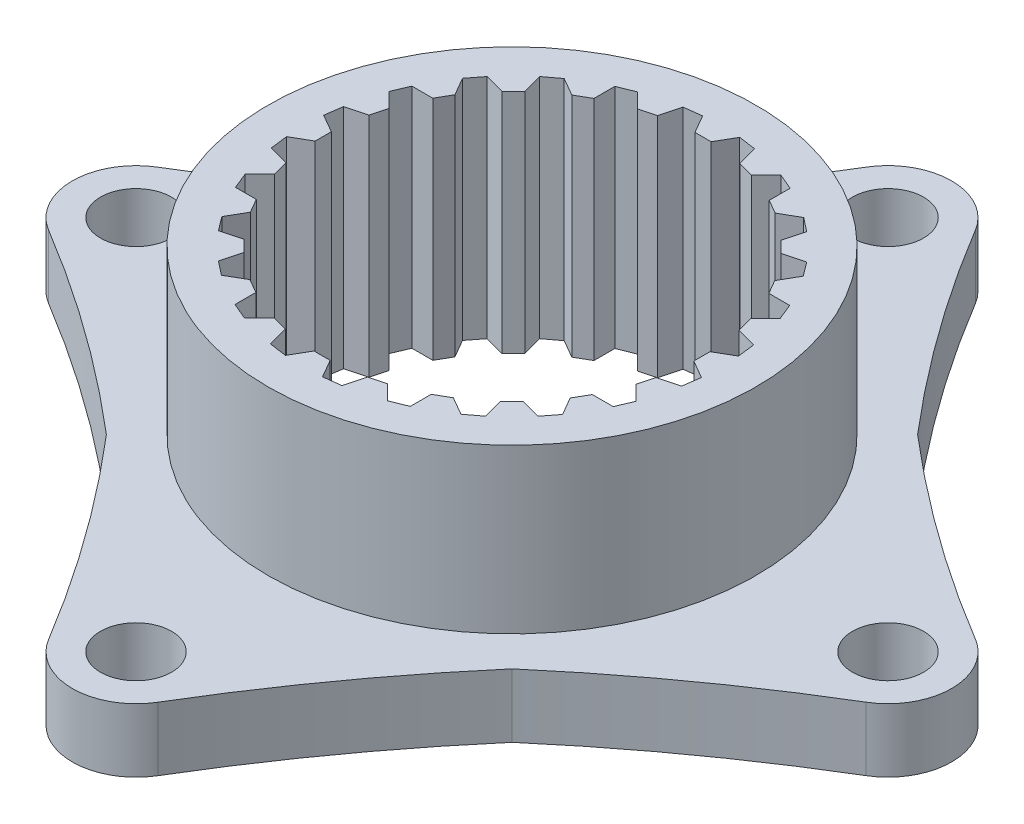
SolidWorks part; units mm, degrees
ref_plane "Front Plane" through (0, 0, 0) normal (0, 0, 1) x (1, 0, 0)
ref_plane "Top Plane" through (0, 0, 0) normal (0, 1, 0) x (1, 0, 0)
ref_plane "Right Plane" through (0, 0, 0) normal (1, 0, 0) x (0, 0, -1)
sketch "Sketch1" plane through (0, 0, 0) normal (0, 1, 0) x (1, 0, 0)
  line L0 (274.6284, 454.6081) -> (780.6456, 454.6081) construction
  circle A0 centre (0, 0) radius 23
  dimension "D1" = 46
sketch "Sketch5" plane through (0, 0, 0) normal (0, 1, 0) x (1, 0, 0)
  circle A0 centre (0, 0) radius 23
  circle A1 centre (0, 0) radius 25
  dimension "D1" = 46
  dimension "D2" = 50
sketch "Sketch6" plane through (0, 0, 0) normal (0, 1, 0) x (1, 0, 0)
  line L0 (-0.9689, -22.7363) -> (0.9689, -22.7363)
  line L1 (0.9689, -22.7363) -> (2.2189, -24.9013)
  line L2 (0, 33.3652) -> (0, -36.4848) construction
  line L3 (-0.9689, -22.7363) -> (-2.2189, -24.9013)
  line L4 (-4.9456, -22.1943) -> (-4.2985, -24.6091)
  line L5 (-6.8174, -21.6927) -> (-4.9456, -22.1943)
  line L6 (-6.8174, -21.6927) -> (-8.5852, -23.4605)
  line L7 (-10.5182, -22.6399) -> (-8.5852, -23.4605)
  line L8 (-10.5182, -20.1399) -> (-10.5182, -22.6399)
  line L9 (-12.1965, -19.171) -> (-10.5182, -20.1399)
  line L10 (-12.1965, -19.171) -> (-14.3615, -20.421)
  line L11 (-16.0164, -19.1281) -> (-14.3615, -20.421)
  line L12 (-15.3693, -16.7133) -> (-16.0164, -19.1281)
  line L13 (-16.7396, -15.343) -> (-15.3693, -16.7133)
  line L14 (-16.7396, -15.343) -> (-19.1544, -15.99)
  line L15 (-20.4182, -14.3129) -> (-19.1544, -15.99)
  line L16 (-19.1682, -12.1478) -> (-20.4182, -14.3129)
  line L17 (-20.1372, -10.4696) -> (-19.1682, -12.1478)
  line L18 (-20.1372, -10.4696) -> (-22.6372, -10.4696)
  line L19 (-23.4239, -8.5225) -> (-22.6372, -10.4696)
  line L20 (-21.6561, -6.7547) -> (-23.4239, -8.5225)
  line L21 (-22.1576, -4.8829) -> (-21.6561, -6.7547)
  line L22 (-22.1576, -4.8829) -> (-24.5725, -4.2358)
  line L23 (-24.8284, -2.1515) -> (-24.5725, -4.2358)
  line L24 (-22.6633, -0.9015) -> (-24.8284, -2.1515)
  line L25 (-22.6633, 1.0364) -> (-22.6633, -0.9015)
  line L26 (-22.6633, 1.0364) -> (-24.8284, 2.2864)
  line L27 (-24.5361, 4.366) -> (-24.8284, 2.2864)
  line L28 (-22.1213, 5.013) -> (-24.5361, 4.366)
  line L29 (-21.6197, 6.8849) -> (-22.1213, 5.013)
  line L30 (-21.6197, 6.8849) -> (-23.3875, 8.6526)
  line L31 (-22.567, 10.5857) -> (-23.3875, 8.6526)
  line L32 (-20.067, 10.5857) -> (-22.567, 10.5857)
  line L33 (-19.098, 12.2639) -> (-20.067, 10.5857)
  line L34 (-19.098, 12.2639) -> (-20.348, 14.429)
  line L35 (-19.0552, 16.0838) -> (-20.348, 14.429)
  line L36 (-16.6403, 15.4368) -> (-19.0552, 16.0838)
  line L37 (-15.27, 16.8071) -> (-16.6403, 15.4368)
  line L38 (-15.27, 16.8071) -> (-15.9171, 19.2219)
  line L39 (-14.24, 20.4857) -> (-15.9171, 19.2219)
  line L40 (-12.0749, 19.2357) -> (-14.24, 20.4857)
  line L41 (-10.3966, 20.2046) -> (-12.0749, 19.2357)
  line L42 (-10.3966, 20.2046) -> (-10.3966, 22.7046)
  line L43 (-8.4496, 23.4913) -> (-10.3966, 22.7046)
  line L44 (-6.6818, 21.7235) -> (-8.4496, 23.4913)
  line L45 (-4.8099, 22.2251) -> (-6.6818, 21.7235)
  line L46 (-4.8099, 22.2251) -> (-4.1629, 24.6399)
  line L47 (-2.0785, 24.8958) -> (-4.1629, 24.6399)
  line L48 (-0.8285, 22.7308) -> (-2.0785, 24.8958)
  line L49 (1.1093, 22.7308) -> (-0.8285, 22.7308)
  line L50 (1.1093, 22.7308) -> (2.3593, 24.8958)
  line L51 (4.4389, 24.6036) -> (2.3593, 24.8958)
  line L52 (5.086, 22.1888) -> (4.4389, 24.6036)
  line L53 (6.9578, 21.6872) -> (5.086, 22.1888)
  line L54 (6.9578, 21.6872) -> (8.7256, 23.455)
  line L55 (10.6586, 22.6344) -> (8.7256, 23.455)
  line L56 (10.6586, 20.1344) -> (10.6586, 22.6344)
  line L57 (12.3369, 19.1655) -> (10.6586, 20.1344)
  line L58 (12.3369, 19.1655) -> (14.5019, 20.4155)
  line L59 (16.1568, 19.1226) -> (14.5019, 20.4155)
  line L60 (15.5097, 16.7078) -> (16.1568, 19.1226)
  line L61 (16.88, 15.3375) -> (15.5097, 16.7078)
  line L62 (16.88, 15.3375) -> (19.2948, 15.9845)
  line L63 (20.5586, 14.3074) -> (19.2948, 15.9845)
  line L64 (19.3086, 12.1424) -> (20.5586, 14.3074)
  line L65 (20.2776, 10.4641) -> (19.3086, 12.1424)
  line L66 (20.2776, 10.4641) -> (22.7776, 10.4641)
  line L67 (23.5643, 8.517) -> (22.7776, 10.4641)
  line L68 (21.7965, 6.7492) -> (23.5643, 8.517)
  line L69 (22.298, 4.8774) -> (21.7965, 6.7492)
  line L70 (22.298, 4.8774) -> (24.7129, 4.2303)
  line L71 (24.9688, 2.146) -> (24.7129, 4.2303)
  line L72 (22.8037, 0.896) -> (24.9688, 2.146)
  line L73 (22.8037, -1.0419) -> (22.8037, 0.896)
  line L74 (22.8037, -1.0419) -> (24.9688, -2.2919)
  line L75 (24.6765, -4.3714) -> (24.9688, -2.2919)
  line L76 (22.2617, -5.0185) -> (24.6765, -4.3714)
  line L77 (21.7601, -6.8903) -> (22.2617, -5.0185)
  line L78 (21.7601, -6.8903) -> (23.5279, -8.6581)
  line L79 (22.7074, -10.5912) -> (23.5279, -8.6581)
  line L80 (20.2074, -10.5912) -> (22.7074, -10.5912)
  line L81 (19.2384, -12.2694) -> (20.2074, -10.5912)
  line L82 (19.2384, -12.2694) -> (20.4884, -14.4345)
  line L83 (19.1955, -16.0893) -> (20.4884, -14.4345)
  line L84 (16.7807, -15.4423) -> (19.1955, -16.0893)
  line L85 (15.4104, -16.8126) -> (16.7807, -15.4423)
  line L86 (15.4104, -16.8126) -> (16.0575, -19.2274)
  line L87 (14.3804, -20.4912) -> (16.0575, -19.2274)
  line L88 (12.2153, -19.2412) -> (14.3804, -20.4912)
  line L89 (10.537, -20.2101) -> (12.2153, -19.2412)
  line L90 (10.537, -20.2101) -> (10.537, -22.7101)
  line L91 (8.59, -23.4968) -> (10.537, -22.7101)
  line L92 (6.8222, -21.729) -> (8.59, -23.4968)
  line L93 (4.9503, -22.2306) -> (6.8222, -21.729)
  line L94 (4.9503, -22.2306) -> (4.3033, -24.6454)
  line L95 (2.2189, -24.9013) -> (4.3033, -24.6454)
  line L96 (-4.2985, -24.6091) -> (-2.2189, -24.9013)
  circle A0 centre (0, 0) radius 23 construction
  circle A1 centre (0, 0) radius 25 construction
  point P11 (0, -23)
  point P131 (0.0702, -0.0027)
  dimension "D4" = 2.5
  dimension "D1" = 2.1
  dimension "D5" = 112
  dimension "D6" = 120
  dimension "D2" = 1.9379
  dimension "D3" = 24
sketch "Sketch8" plane through (0, 0, 0) normal (0, 1, 0) x (1, 0, 0)
  circle A0 centre (0, 0) radius 100
  dimension "D1" = 200
extrude "Boss-Extrude4" add sketch "Sketch8" along normal blind 27.178 contours A0
extrude "Cut-Extrude1" cut sketch "Sketch6" along normal through all
sketch "Sketch9" plane through (0, 27.178, 0) normal (0, 1, 0) x (1, 0, 0)
  ellipse E0 centre (0, 0) end of major axis (-10.2816, -27.3407) minor radius 29.21
  dimension "D1" = 58.42
extrude "Cut-Extrude3" cut sketch "Sketch9" against normal blind 19.558 flip side to cut
sketch "Sketch10" plane through (0, 7.62, 0) normal (0, 1, 0) x (1, 0, 0)
  ellipse E0 centre (45.0088, 0) end of major axis (49.2633, 0) minor radius 4.2545
  ellipse E1 centre (0, 45.0088) end of major axis (0, 49.2633) minor radius 4.2545
  ellipse E2 centre (-45.0088, 0) end of major axis (-49.2633, 0) minor radius 4.2545
  ellipse E3 centre (0, -45.0088) end of major axis (0, -49.2633) minor radius 4.2545
  point P28 (0, 0)
  dimension "D1" = 4
  dimension "D2" = 45.0088
  dimension "D3" = 8.509
extrude "Cut-Extrude4" cut sketch "Sketch10" against normal blind 7.62 contours E1 | E0 | E2 | E3
sketch "Sketch11" plane through (0, 7.62, 0) normal (0, 1, 0) x (1, 0, 0)
  line L0 (0.003, -45.0088) -> (45.0088, 0.003) construction
  line L1 (0, 0) -> (70.6264, -70.6168) construction
  arc A0 (6.5389, -48.9263) -> (24.2772, -24.2739) centre (162.2578, -142.2634) cw
  arc A1 (48.9272, -6.5323) -> (24.2772, -24.2739) centre (142.2854, -162.2385) ccw
  arc A2 (-6.5323, -48.9272) -> (-24.2739, -24.2772) centre (-162.2385, -142.2854) ccw
  arc A3 (-48.9263, -6.5389) -> (-24.2739, -24.2772) centre (-142.2634, -162.2578) cw
  arc A4 (-48.9272, 6.5323) -> (-24.2772, 24.2739) centre (-142.2854, 162.2385) ccw
  arc A5 (-6.5389, 48.9263) -> (-24.2772, 24.2739) centre (-162.2578, 142.2634) cw
  arc A6 (6.5323, 48.9272) -> (24.2739, 24.2772) centre (162.2385, 142.2854) ccw
  arc A7 (48.9263, 6.5389) -> (24.2739, 24.2772) centre (142.2634, 162.2578) cw
  ellipse E0 centre (0.003, -45.0088) end of major axis (0.003, -37.3888) minor radius 7.62
  ellipse E1 centre (-45.0088, -0.003) end of major axis (-37.3888, -0.003) minor radius 7.62
  ellipse E2 centre (-0.003, 45.0088) end of major axis (-0.003, 37.3888) minor radius 7.62
  ellipse E3 centre (45.0088, 0.003) end of major axis (45.0088, 7.623) minor radius 7.62
  point P27 (0, 0)
  point P51 (0, 0)
  circle M10 centre (0, 0) radius 100
  dimension "D4" = 181.5494
  dimension "D1" = 4
  dimension "D2" = 15.24
  dimension "D3" = 4
extrude "Cut-Extrude5" cut sketch "Sketch11" against normal blind 7.62 contours E3 A1 A0 E0 A2 A3 E1 A4 A5 E2 A6 A7 M10 region at (-97.1716, 7.62, 0)
